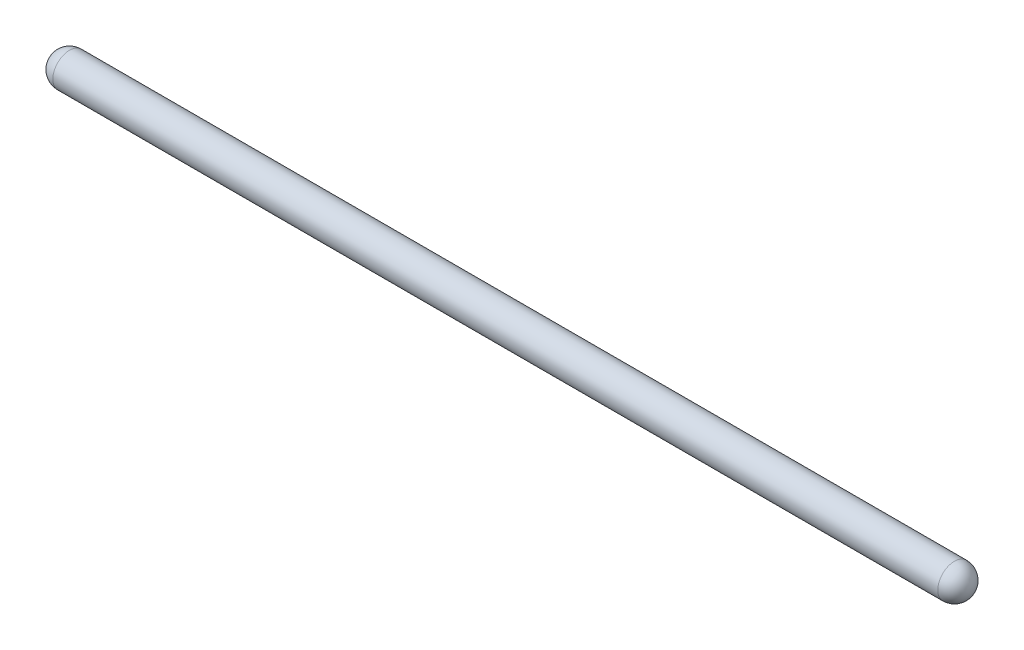
SolidWorks part; units mm, degrees
material "Brass"
ref_plane "Front Plane" through (0, 0, 0) normal (0, 0, 1) x (1, 0, 0)
ref_plane "Top Plane" through (0, 0, 0) normal (0, 1, 0) x (1, 0, 0)
ref_plane "Right Plane" through (0, 0, 0) normal (1, 0, 0) x (0, 0, -1)
sketch "Sketch1" plane through (0, 0, 0) normal (0, 0, 1) x (1, 0, 0)
  line L0 (0, 0) -> (165, 0) construction
  line L1 (3, 3) -> (162, 3)
  line L2 (165, 0) -> (0, 0)
  arc A0 (165, 0) -> (162, 3) centre (162, 0) ccw
  arc A1 (3, 3) -> (0, 0) centre (3, 0) ccw
  dimension "D3" = 3
  dimension "D1" = 3
  dimension "D2" = 162
revolve "Revolve1" add sketch "Sketch1" angle 360 about L0
